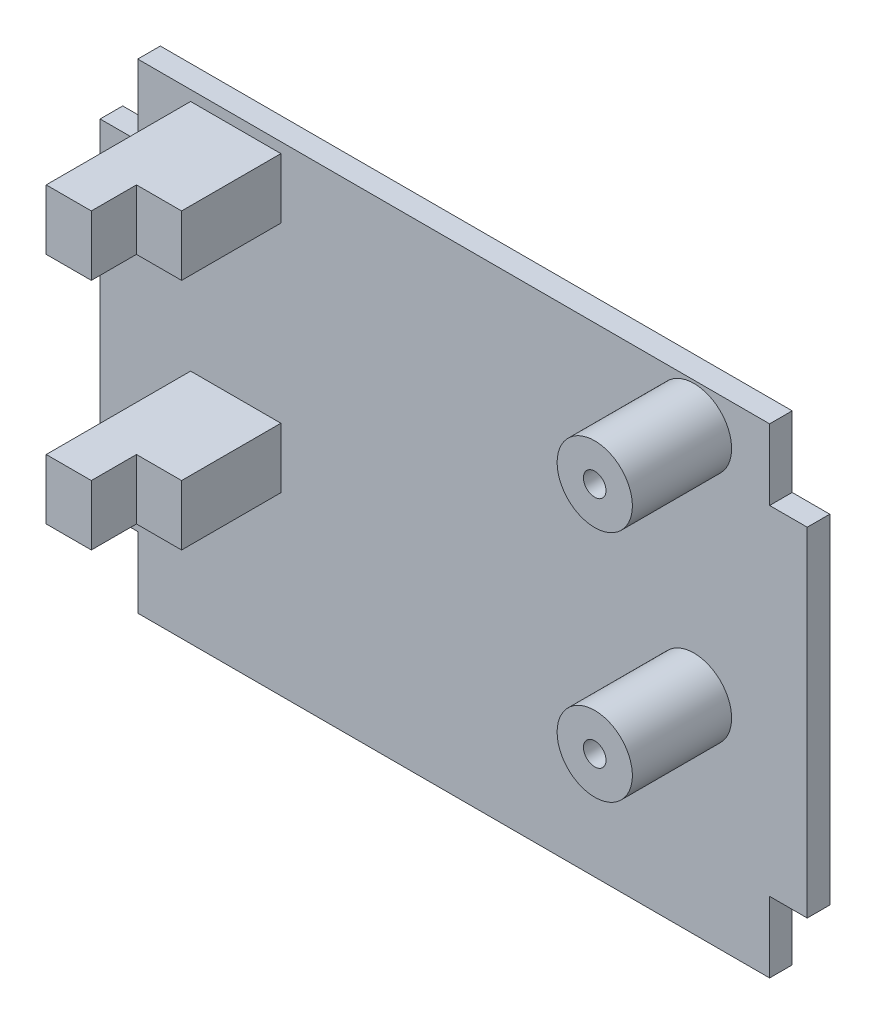
SolidWorks part; units mm, degrees
ref_plane "Plan de face" through (0, 0, 0) normal (0, 0, 1) x (1, 0, 0)
ref_plane "Plan de dessus" through (0, 0, 0) normal (0, 1, 0) x (1, 0, 0)
ref_plane "Plan de droite" through (0, 0, 0) normal (1, 0, 0) x (0, 0, -1)
sketch "Esquisse1" plane through (0, 0, 0) normal (0, 0, 1) x (1, 0, 0)
  line L1 (0, 0) -> (47, 0)
  line L2 (0, 0) -> (0, 31.9)
  line L3 (0, 31.9) -> (47, 31.9)
  line L4 (47, 0) -> (47, 31.9)
  dimension "D1" = 31.9
  dimension "D2" = 47
extrude "Boss.-Extru.1" add sketch "Esquisse1" along normal blind 1.5
sketch "Esquisse2" plane through (0, 0, 1.5) normal (0, 0, 1) x (1, 0, 0)
  line L0 (23.5, 31.9) -> (23.5, 0) construction
  line L1 (47, 31.9) -> (44.5, 31.9)
  line L2 (47, 31.9) -> (47, 27.2)
  line L3 (47, 27.2) -> (44.5, 27.2)
  line L4 (44.5, 31.9) -> (44.5, 27.2)
  line L5 (47, 31.9) -> (0, 31.9) construction
  line L6 (0, 0) -> (47, 0) construction
  line L8 (47, 15.95) -> (0, 15.95) construction
  line L9 (47, 0) -> (47, 31.9) construction
  line L10 (0, 31.9) -> (0, 0) construction
  line L11 (47, 4.7) -> (44.5, 4.7)
  line L12 (44.5, 0) -> (44.5, 4.7)
  line L13 (47, 0) -> (44.5, 0)
  line L14 (47, 0) -> (47, 4.7)
  line L15 (0, 0) -> (0, 4.7)
  line L16 (0, 0) -> (2.5, 0)
  line L17 (2.5, 0) -> (2.5, 4.7)
  line L18 (0, 4.7) -> (2.5, 4.7)
  line L19 (0, 27.2) -> (2.5, 27.2)
  line L20 (2.5, 31.9) -> (2.5, 27.2)
  line L21 (0, 31.9) -> (2.5, 31.9)
  line L22 (0, 31.9) -> (0, 27.2)
  dimension "D1" = 4.7
  dimension "D2" = 2.5
extrude "Enlèv. mat.-Extru.1" cut sketch "Esquisse2" against normal through all
sketch "Esquisse3" plane through (0, 0, 1.5) normal (0, 0, 1) x (1, 0, 0)
  line L0 (9.014, 11.6925) -> (9.014, 31.2125) construction
  line L1 (6.014, 31.2125) -> (12.014, 31.2125)
  line L2 (6.014, 31.2125) -> (6.014, 27.2125)
  line L3 (6.014, 27.2125) -> (12.014, 27.2125)
  line L4 (12.014, 31.2125) -> (12.014, 27.2125)
  line L5 (39.514, 11.6925) -> (39.514, 31.2125) construction
  line L6 (7.054, 21.4525) -> (39.514, 21.4525) construction
  line L7 (7.054, 31.2125) -> (7.054, 11.6925) construction
  line L8 (6.014, 15.6925) -> (12.014, 15.6925)
  line L9 (12.014, 11.6925) -> (12.014, 15.6925)
  line L10 (6.014, 11.6925) -> (12.014, 11.6925)
  line L11 (6.014, 11.6925) -> (6.014, 15.6925)
  line L12 (41.474, 31.2125) -> (9.014, 31.2125) construction
  circle A0 centre (39.474, 29.2125) radius 2.5
  circle A2 centre (39.474, 13.6925) radius 2.5
  circle A3 centre (39.474, 29.2125) radius 1 construction
  dimension "D1" = 3
  dimension "D2" = 5
  dimension "D3" = 6
  dimension "D5" = 4
extrude "Boss.-Extru.2" add sketch "Esquisse3" along normal up to surface (6.5991 mm away)
sketch "Esquisse4" plane through (0, 0, 8.0991) normal (0, 0, 1) x (1, 0, 0)
  line L0 (12.014, 27.2125) -> (6.014, 27.2125) construction
  line L1 (6.014, 31.2125) -> (9.014, 31.2125)
  line L2 (6.014, 31.2125) -> (6.014, 27.2125)
  line L3 (6.014, 27.2125) -> (9.014, 27.2125)
  line L4 (9.014, 31.2125) -> (9.014, 27.2125)
  line L5 (6.014, 31.2125) -> (12.014, 31.2125) construction
  line L6 (7.054, 21.4525) -> (39.514, 21.4525) construction
  line L7 (7.054, 31.2125) -> (7.054, 11.6925) construction
  line L8 (39.514, 11.6925) -> (39.514, 31.2125) construction
  line L9 (6.014, 15.6925) -> (9.014, 15.6925)
  line L10 (9.014, 11.6925) -> (9.014, 15.6925)
  line L11 (6.014, 11.6925) -> (9.014, 11.6925)
  line L12 (6.014, 11.6925) -> (6.014, 15.6925)
  line L13 (6.014, 27.2125) -> (6.014, 31.2125) construction
  circle A0 centre (39.474, 29.2125) radius 0.75
  circle A1 centre (39.474, 13.6925) radius 0.75
  line M1 (6.014, 27.2125) -> (12.014, 27.2125)
  line M3 (12.014, 31.2125) -> (6.014, 31.2125)
  line M4 (6.014, 31.2125) -> (6.014, 27.2125)
  dimension "D1" = 1.5
extrude "Boss.-Extru.3" add sketch "Esquisse4" along normal blind 3 contours L11 L12 L9 L10 | L4 M3 M4 M1 | L12 L11 L10 L9 region at (7.514, 29.2125, 8.0991) region at (7.514, 13.6925, 8.0991)
extrude "Enlèv. mat.-Extru.2" cut sketch "Esquisse4<3>" against normal blind 5 contours A0 | A1 region at (39.474, 29.2125, 8.0991) region at (39.474, 13.6925, 8.0991)
sketch "Esquisse4<3>" plane through (0, 0, 8.0991) normal (0, 0, 1) x (1, 0, 0) same geometry as "Esquisse4"
